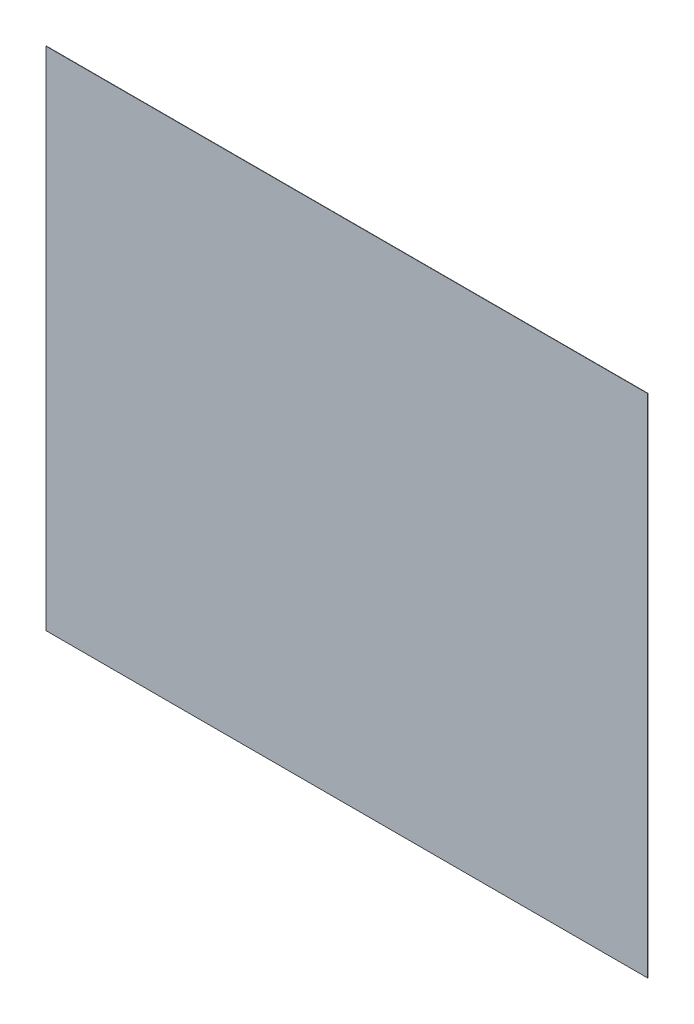
SolidWorks part; units mm, degrees
ref_plane "Front Plane" through (0, 0, 0) normal (0, 0, 1) x (1, 0, 0)
ref_plane "Top Plane" through (0, 0, 0) normal (0, 1, 0) x (1, 0, 0)
ref_plane "Right Plane" through (0, 0, 0) normal (1, 0, 0) x (0, 0, -1)
sketch "Sketch1" plane through (0, 0, 0) normal (0, 0, 1) x (1, 0, 0)
  line L1 (0, 0) -> (1931, 0)
  line L2 (0, 0) -> (0, 1625)
  line L3 (0, 1625) -> (1931, 1625)
  line L4 (1931, 0) -> (1931, 1625)
  dimension "D1" = 1931
  dimension "D2" = 1625
extrude "Boss-Extrude1" add sketch "Sketch1" along normal blind 1
